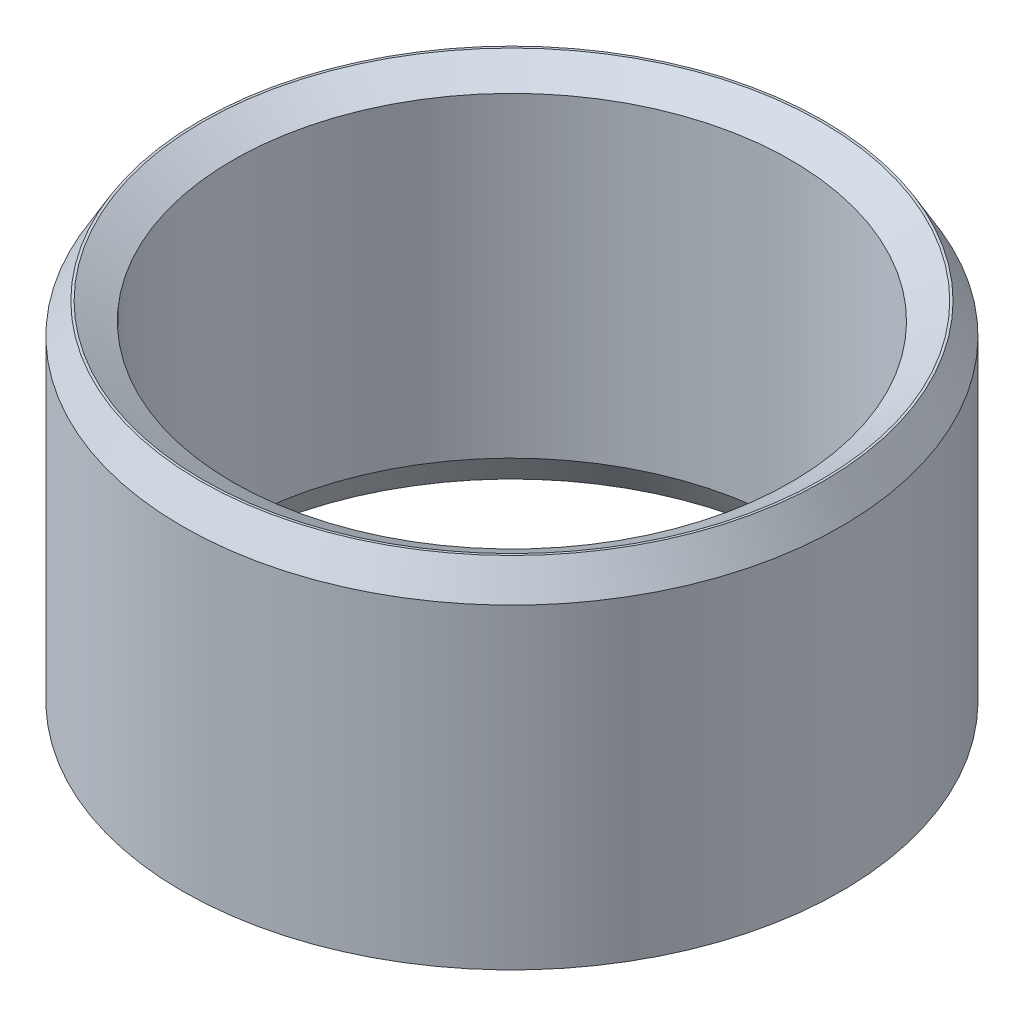
SolidWorks part; units mm, degrees
ref_plane "Front Plane" through (0, 0, 0) normal (0, 0, 1) x (1, 0, 0)
ref_plane "Top Plane" through (0, 0, 0) normal (0, 1, 0) x (1, 0, 0)
ref_plane "Right Plane" through (0, 0, 0) normal (1, 0, 0) x (0, 0, -1)
sketch "Sketch1" plane through (0, 0, 0) normal (0, 1, 0) x (1, 0, 0)
  circle A0 centre (0, 0) radius 40
  dimension "SLEEVE_OD" = 80
extrude "Boss-Extrude1" add sketch "Sketch1" along normal blind 44.1923
sketch "Sketch2" plane through (0, 0, 0) normal (0, 1, 0) x (1, 0, 0)
  circle A0 centre (0, 0) radius 33.8658
  dimension "BORE_D" = 67.7317
extrude "Cut-Extrude1" cut sketch "Sketch2" along normal through all
chamfer "Chamfer1" distance 3.7096 angle 30 4 edges at (0, 44.1923, 33.8658) (0, 0, 33.8658) (0, 0, 40) (0, 44.1923, 40) first distance on face at (0, 44.1923, 33.8658) first distance on face at (0, 0, 33.8658) first distance on face at (0, 44.1923, 40)
